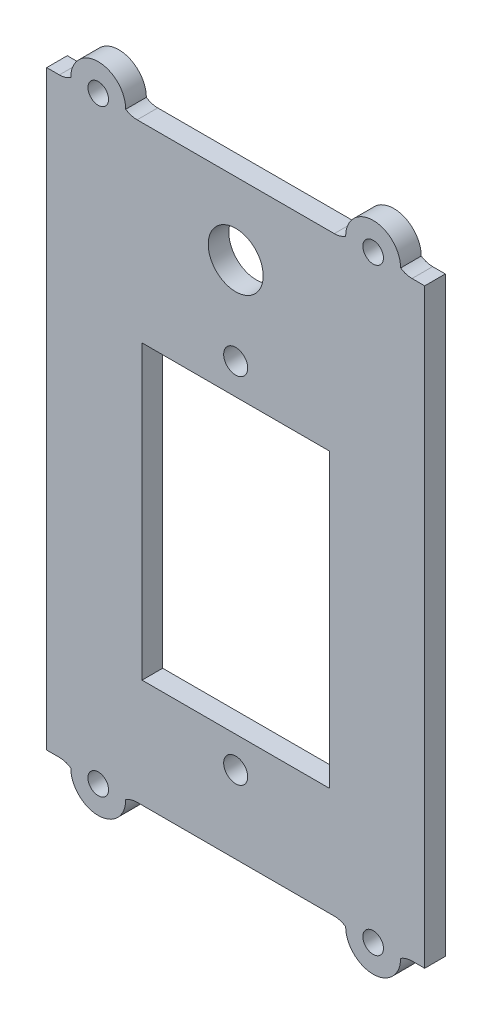
SolidWorks part; units mm, degrees
material "Aircraft Ply"
ref_plane "Front Plane" through (0, 0, 0) normal (0, 0, 1) x (1, 0, 0)
ref_plane "Top Plane" through (0, 0, 0) normal (0, 1, 0) x (1, 0, 0)
ref_plane "Right Plane" through (0, 0, 0) normal (1, 0, 0) x (0, 0, -1)
sketch "Sketch1" plane through (0, 0, 0) normal (0, 0, 1) x (1, 0, 0)
  line L10 (-10.6583, 43) -> (10.6583, 43)
  line L11 (-10.6583, -43) -> (10.6583, -43)
  line L14 (10.6583, -43) -> (14.3417, -43)
  line L15 (25.6583, -43) -> (27.5, -43)
  line L16 (27.5, -43) -> (27.5, 43)
  line L17 (27.5, 43) -> (25.6583, 43)
  line L18 (14.3417, 43) -> (10.6583, 43)
  line L20 (-10.6583, 43) -> (-14.3417, 43)
  line L21 (-25.6583, 43) -> (-27.5, 43)
  line L22 (-27.5, 43) -> (-27.5, -43)
  line L23 (-27.5, -43) -> (-25.6583, -43)
  line L24 (-14.3417, -43) -> (-10.6583, -43)
  line L26 (10.6583, -43) -> (14.3417, -43)
  line L27 (25.6583, -43) -> (27.5, -43)
  line L28 (27.5, -43) -> (27.5, 43)
  line L29 (27.5, 43) -> (25.6583, 43)
  line L30 (14.3417, 43) -> (10.6583, 43)
  line L32 (-10.6583, 43) -> (-14.3417, 43)
  line L33 (-25.6583, 43) -> (-27.5, 43)
  line L34 (-27.5, 43) -> (-27.5, -43)
  line L35 (-27.5, -43) -> (-25.6583, -43)
  line L36 (-14.3417, -43) -> (-10.6583, -43)
  circle A0 centre (-20, 43.5) radius 1.5
  circle A3 centre (20, 43.5) radius 1.5
  circle A4 centre (-20, -43.5) radius 1.5
  circle A7 centre (20, -43.5) radius 1.5
  arc A24 (-9, -43.5) -> (-1, -43.5) centre (-5, -43.5) ccw
  arc A25 (0, -43.0731) -> (-1, -43.5) centre (0.6583, -46) ccw
  arc A26 (1, -43.5) -> (0, -43.0731) centre (-0.6583, -46) ccw
  arc A27 (1, -43.5) -> (9, -43.5) centre (5, -43.5) ccw
  arc A28 (10.6583, -43) -> (9, -43.5) centre (10.6583, -46) ccw
  arc A29 (16, -43.5) -> (14.3417, -43) centre (14.3417, -46) ccw
  arc A30 (16, -43.5) -> (24, -43.5) centre (20, -43.5) ccw
  arc A31 (25.6583, -43) -> (24, -43.5) centre (25.6583, -46) ccw
  arc A32 (24, 43.5) -> (25.6583, 43) centre (25.6583, 46) ccw
  arc A33 (24, 43.5) -> (16, 43.5) centre (20, 43.5) ccw
  arc A34 (14.3417, 43) -> (16, 43.5) centre (14.3417, 46) ccw
  arc A35 (9, 43.5) -> (10.6583, 43) centre (10.6583, 46) ccw
  arc A36 (9, 43.5) -> (1, 43.5) centre (5, 43.5) ccw
  arc A37 (0, 43.0731) -> (1, 43.5) centre (-0.6583, 46) ccw
  arc A38 (-1, 43.5) -> (0, 43.0731) centre (0.6583, 46) ccw
  arc A39 (-1, 43.5) -> (-9, 43.5) centre (-5, 43.5) ccw
  arc A40 (-10.6583, 43) -> (-9, 43.5) centre (-10.6583, 46) ccw
  arc A41 (-16, 43.5) -> (-14.3417, 43) centre (-14.3417, 46) ccw
  arc A42 (-16, 43.5) -> (-24, 43.5) centre (-20, 43.5) ccw
  arc A43 (-25.6583, 43) -> (-24, 43.5) centre (-25.6583, 46) ccw
  arc A44 (-24, -43.5) -> (-25.6583, -43) centre (-25.6583, -46) ccw
  arc A45 (-24, -43.5) -> (-16, -43.5) centre (-20, -43.5) ccw
  arc A46 (-14.3417, -43) -> (-16, -43.5) centre (-14.3417, -46) ccw
  arc A47 (-9, -43.5) -> (-10.6583, -43) centre (-10.6583, -46) ccw
  arc A48 (-9, -43.5) -> (-1, -43.5) centre (-5, -43.5) ccw
  arc A49 (0, -43.0731) -> (-1, -43.5) centre (0.6583, -46) ccw
  arc A50 (1, -43.5) -> (0, -43.0731) centre (-0.6583, -46) ccw
  arc A51 (1, -43.5) -> (9, -43.5) centre (5, -43.5) ccw
  arc A52 (10.6583, -43) -> (9, -43.5) centre (10.6583, -46) ccw
  arc A53 (16, -43.5) -> (14.3417, -43) centre (14.3417, -46) ccw
  arc A54 (16, -43.5) -> (24, -43.5) centre (20, -43.5) ccw
  arc A55 (25.6583, -43) -> (24, -43.5) centre (25.6583, -46) ccw
  arc A56 (24, 43.5) -> (25.6583, 43) centre (25.6583, 46) ccw
  arc A57 (24, 43.5) -> (16, 43.5) centre (20, 43.5) ccw
  arc A58 (14.3417, 43) -> (16, 43.5) centre (14.3417, 46) ccw
  arc A59 (9, 43.5) -> (10.6583, 43) centre (10.6583, 46) ccw
  arc A60 (9, 43.5) -> (1, 43.5) centre (5, 43.5) ccw
  arc A61 (0, 43.0731) -> (1, 43.5) centre (-0.6583, 46) ccw
  arc A62 (-1, 43.5) -> (0, 43.0731) centre (0.6583, 46) ccw
  arc A63 (-1, 43.5) -> (-9, 43.5) centre (-5, 43.5) ccw
  arc A64 (-10.6583, 43) -> (-9, 43.5) centre (-10.6583, 46) ccw
  arc A65 (-16, 43.5) -> (-14.3417, 43) centre (-14.3417, 46) ccw
  arc A66 (-16, 43.5) -> (-24, 43.5) centre (-20, 43.5) ccw
  arc A67 (-25.6583, 43) -> (-24, 43.5) centre (-25.6583, 46) ccw
  arc A68 (-24, -43.5) -> (-25.6583, -43) centre (-25.6583, -46) ccw
  arc A69 (-24, -43.5) -> (-16, -43.5) centre (-20, -43.5) ccw
  arc A70 (-14.3417, -43) -> (-16, -43.5) centre (-14.3417, -46) ccw
  arc A71 (-9, -43.5) -> (-10.6583, -43) centre (-10.6583, -46) ccw
  dimension "D2" = 3
  dimension "D1" = 0
extrude "Boss-Extrude1" add sketch "Sketch1" along normal blind 3 contours A70 L36 L11 L26 A53 A54 A55 L27 L28 L29 A56 A57 A58 L30 L10 L32 A65 A66 A67 L33 L34 L35 A68 A69 A7 A4 A3 A0 region at (0, 0, 0)
sketch "Sketch2" plane through (0, 0, 0) normal (0, 0, 1) x (1, 0, 0)
  line L0 (0, 0) -> (0, 32.5) construction
  line L1 (0, 0) -> (0, -44.7304) construction
  line L4 (-13.625, 15.25) -> (13.625, 15.25)
  line L5 (-13.625, 15.25) -> (-13.625, -27.25)
  line L6 (-13.625, -27.25) -> (13.625, -27.25)
  line L7 (13.625, 15.25) -> (13.625, -27.25)
  line L8 (-13.625, 15.25) -> (13.625, -27.25) construction
  line L9 (-13.625, -27.25) -> (13.625, 15.25) construction
  circle A0 centre (0, 32.5) radius 4
  circle A1 centre (0, 19.75) radius 1.75
  circle A2 centre (0, -31.75) radius 1.75
  point P4 (0, -6)
  dimension "D1" = 8
  dimension "D8" = 3.5
  dimension "D2" = 32.5
  dimension "D3" = 42.5
  dimension "D4" = 27.25
  dimension "D5" = 6
  dimension "D6" = 4.5
  dimension "D7" = 4.5
extrude "Cut-Extrude1" cut sketch "Sketch2" along normal through all
